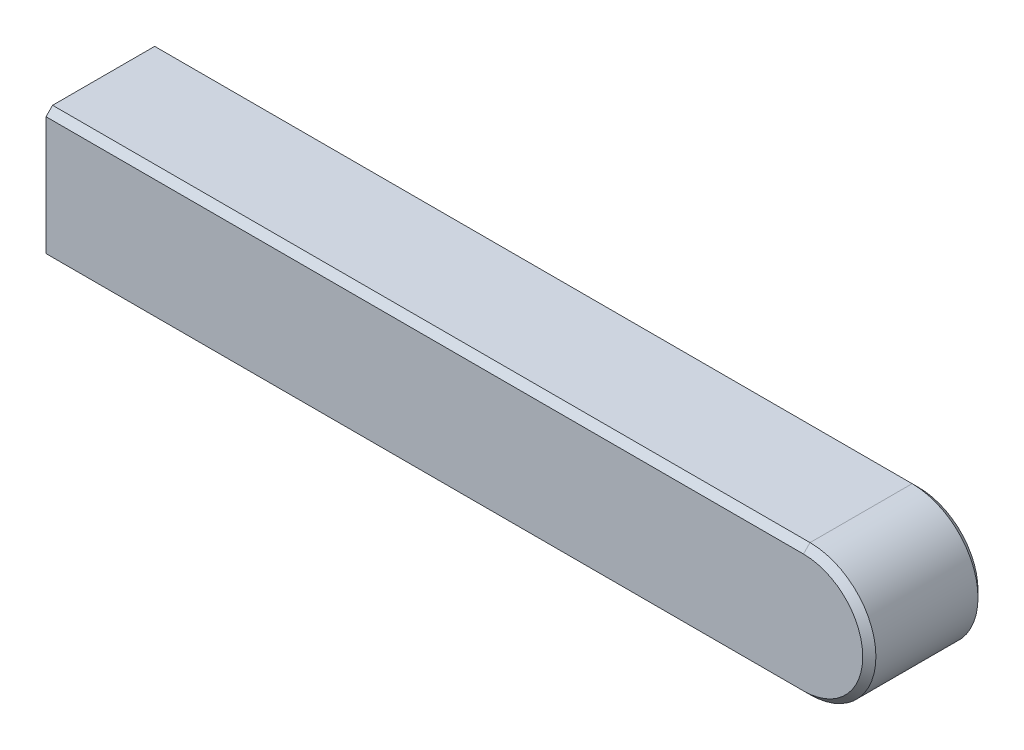
SolidWorks part; units mm, degrees
ref_plane "Front" through (0, 0, 0) normal (0, 0, 1) x (1, 0, 0)
ref_plane "Top" through (0, 0, 0) normal (0, 1, 0) x (1, 0, 0)
ref_plane "Right" through (0, 0, 0) normal (1, 0, 0) x (0, 0, -1)
sketch "body" plane through (0, 0, 0) normal (0, 0, 1) x (1, 0, 0)
  line L1 (0, 0) -> (46, 0)
  line L2 (0, 0) -> (0, 8)
  line L3 (0, 8) -> (46, 8)
  arc A0 (46, 8) -> (46, 0) centre (46, 4) cw
  dimension "Width" = 8
  dimension "Length" = 50
extrude "Extrude1" add sketch "body" along normal blind 7
chamfer "Chamfer1" distance 0.4 6 edges at (23, 0, 0) (50, 4, 0) (23, 8, 0) (23, 0, 7) (50, 4, 7) (23, 8, 7)
